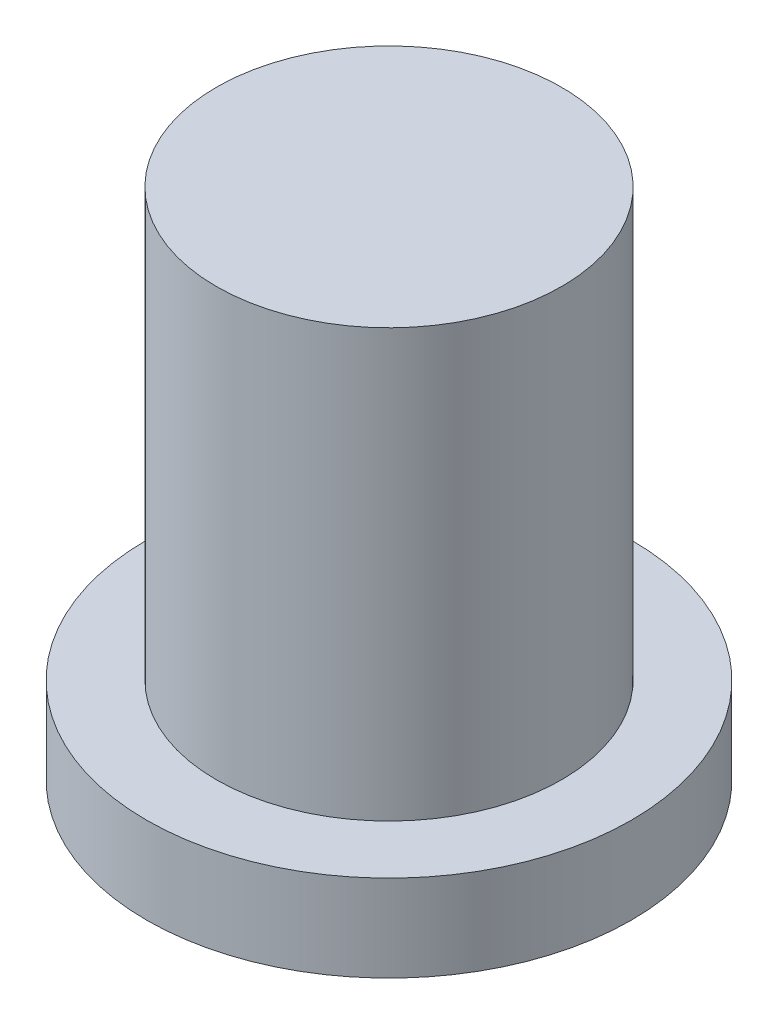
SolidWorks part; units mm, degrees
ref_plane "Alzado" through (0, 0, 0) normal (0, 0, 1) x (1, 0, 0)
ref_plane "Planta" through (0, 0, 0) normal (0, 1, 0) x (1, 0, 0)
ref_plane "Vista lateral" through (0, 0, 0) normal (1, 0, 0) x (0, 0, -1)
sketch "Croquis1" plane through (0, 0, 0) normal (0, 1, 0) x (1, 0, 0)
  circle A0 centre (0, 0) radius 21
  dimension "D1" = 42
extrude "Saliente-Extruir1" add sketch "Croquis1" along normal blind 7.5
sketch "Croquis2" plane through (0, 7.5, 0) normal (0, 1, 0) x (1, 0, 0)
  circle A0 centre (0, 0) radius 14.95
  dimension "D1" = 29.9
extrude "Saliente-Extruir2" add sketch "Croquis2" along normal blind 37
sketch "Croquis3" plane through (0, 0, 0) normal (0, -1, 0) x (1, 0, 0)
  line L0 (-4.995, -4.6152) -> (-7.8942, -4.9562) construction
  line L1 (-4.6152, 4.995) -> (-4.9562, 7.8942) construction
  line L2 (-5.9296, 3.3301) -> (-8.8288, 2.989) construction
  line L3 (-8.8288, 2.989) -> (-18.0646, 0.36) construction
  line L4 (-7.8942, -4.9562) -> (-17.488, -4.5421) construction
  line L5 (-3.3301, -5.9296) -> (-2.989, -8.8288) construction
  line L6 (-2.989, -8.8288) -> (-0.36, -18.0646) construction
  line L7 (4.9562, -7.8942) -> (4.5421, -17.488) construction
  line L8 (4.6152, -4.995) -> (4.9562, -7.8942) construction
  line L9 (5.9296, -3.3301) -> (8.8288, -2.989) construction
  line L10 (8.8288, -2.989) -> (18.0646, -0.36) construction
  line L11 (7.8942, 4.9562) -> (17.488, 4.5421) construction
  line L12 (4.995, 4.6152) -> (7.8942, 4.9562) construction
  line L13 (3.3301, 5.9296) -> (2.989, 8.8288) construction
  line L14 (2.989, 8.8288) -> (0.36, 18.0646) construction
  line L15 (-4.9562, 7.8942) -> (-4.5421, 17.488) construction
  line L16 (-4.995, -4.6152) -> (-7.8942, -4.9562) construction
  line L17 (-4.6152, 4.995) -> (-4.9562, 7.8942) construction
  line L18 (-5.9296, 3.3301) -> (-8.8288, 2.989) construction
  line L19 (-8.8288, 2.989) -> (-18.0646, 0.36) construction
  line L20 (-7.8942, -4.9562) -> (-17.488, -4.5421) construction
  line L21 (-3.3301, -5.9296) -> (-2.989, -8.8288) construction
  line L22 (-2.989, -8.8288) -> (-0.36, -18.0646) construction
  line L23 (4.9562, -7.8942) -> (4.5421, -17.488) construction
  line L24 (4.6152, -4.995) -> (4.9562, -7.8942) construction
  line L25 (5.9296, -3.3301) -> (8.8288, -2.989) construction
  line L26 (8.8288, -2.989) -> (18.0646, -0.36) construction
  line L27 (7.8942, 4.9562) -> (17.488, 4.5421) construction
  line L28 (4.995, 4.6152) -> (7.8942, 4.9562) construction
  line L29 (3.3301, 5.9296) -> (2.989, 8.8288) construction
  line L30 (2.989, 8.8288) -> (0.36, 18.0646) construction
  line L31 (-4.9562, 7.8942) -> (-4.5421, 17.488) construction
  line L32 (-4.9717, -4.8138) -> (-7.8868, -5.1567)
  line L33 (-7.8868, -5.1567) -> (-17.4966, -4.7419)
  line L34 (-8.8681, 3.1858) -> (-18.1194, 0.5524)
  line L35 (-5.953, 3.5287) -> (-8.8681, 3.1858)
  line L36 (-4.8138, 4.9717) -> (-5.1567, 7.8868)
  line L37 (-5.1567, 7.8868) -> (-4.7419, 17.4966)
  line L38 (3.1858, 8.8681) -> (0.5524, 18.1194)
  line L39 (3.5287, 5.953) -> (3.1858, 8.8681)
  line L40 (4.9717, 4.8138) -> (7.8868, 5.1567)
  line L41 (7.8868, 5.1567) -> (17.4966, 4.7419)
  line L42 (8.8681, -3.1858) -> (18.1194, -0.5524)
  line L43 (5.953, -3.5287) -> (8.8681, -3.1858)
  line L44 (4.8138, -4.9717) -> (5.1567, -7.8868)
  line L45 (5.1567, -7.8868) -> (4.7419, -17.4966)
  line L46 (-3.1858, -8.8681) -> (-0.5524, -18.1194)
  line L47 (-3.5287, -5.953) -> (-3.1858, -8.8681)
  arc A0 (-5.9296, 3.3301) -> (-4.6152, 4.995) centre (-6.1049, 4.8198) ccw construction
  arc A1 (-18.0646, 0.36) -> (-17.488, -4.5421) centre (-17.3802, -2.0445) ccw construction
  arc A2 (-3.3301, -5.9296) -> (-4.995, -4.6152) centre (-4.8198, -6.1049) ccw construction
  arc A3 (-0.36, -18.0646) -> (4.5421, -17.488) centre (2.0445, -17.3802) ccw construction
  arc A4 (5.9296, -3.3301) -> (4.6152, -4.995) centre (6.1049, -4.8198) ccw construction
  arc A5 (18.0646, -0.36) -> (17.488, 4.5421) centre (17.3802, 2.0445) ccw construction
  arc A6 (3.3301, 5.9296) -> (4.995, 4.6152) centre (4.8198, 6.1049) ccw construction
  arc A7 (0.36, 18.0646) -> (-4.5421, 17.488) centre (-2.0445, 17.3802) ccw construction
  arc A8 (-5.9296, 3.3301) -> (-4.6152, 4.995) centre (-6.1049, 4.8198) ccw construction
  arc A9 (-18.0646, 0.36) -> (-17.488, -4.5421) centre (-17.3802, -2.0445) ccw construction
  arc A10 (-3.3301, -5.9296) -> (-4.995, -4.6152) centre (-4.8198, -6.1049) ccw construction
  arc A11 (-0.36, -18.0646) -> (4.5421, -17.488) centre (2.0445, -17.3802) ccw construction
  arc A12 (5.9296, -3.3301) -> (4.6152, -4.995) centre (6.1049, -4.8198) ccw construction
  arc A13 (18.0646, -0.36) -> (17.488, 4.5421) centre (17.3802, 2.0445) ccw construction
  arc A14 (3.3301, 5.9296) -> (4.995, 4.6152) centre (4.8198, 6.1049) ccw construction
  arc A15 (0.36, 18.0646) -> (-4.5421, 17.488) centre (-2.0445, 17.3802) ccw construction
  arc A16 (-18.1194, 0.5524) -> (-17.4966, -4.7419) centre (-17.3802, -2.0445) ccw
  arc A17 (-5.953, 3.5287) -> (-4.8138, 4.9717) centre (-6.1049, 4.8198) ccw
  arc A18 (0.5524, 18.1194) -> (-4.7419, 17.4966) centre (-2.0445, 17.3802) ccw
  arc A19 (3.5287, 5.953) -> (4.9717, 4.8138) centre (4.8198, 6.1049) ccw
  arc A20 (18.1194, -0.5524) -> (17.4966, 4.7419) centre (17.3802, 2.0445) ccw
  arc A21 (5.953, -3.5287) -> (4.8138, -4.9717) centre (6.1049, -4.8198) ccw
  arc A22 (-0.5524, -18.1194) -> (4.7419, -17.4966) centre (2.0445, -17.3802) ccw
  arc A23 (-3.5287, -5.953) -> (-4.9717, -4.8138) centre (-4.8198, -6.1049) ccw
  dimension "D1" = 0.2
extrude "Cortar-Extruir1" cut sketch "Croquis3" against normal blind 2.5 and the other way through all
sketch "Croquis4" plane through (0, 2.5, 0) normal (0, -1, 0) x (1, 0, 0)
  circle A0 centre (0, 0) radius 5.5
  dimension "D1" = 11
extrude "Cortar-Extruir2" cut sketch "Croquis4" against normal blind 1.5 and the other way through all
